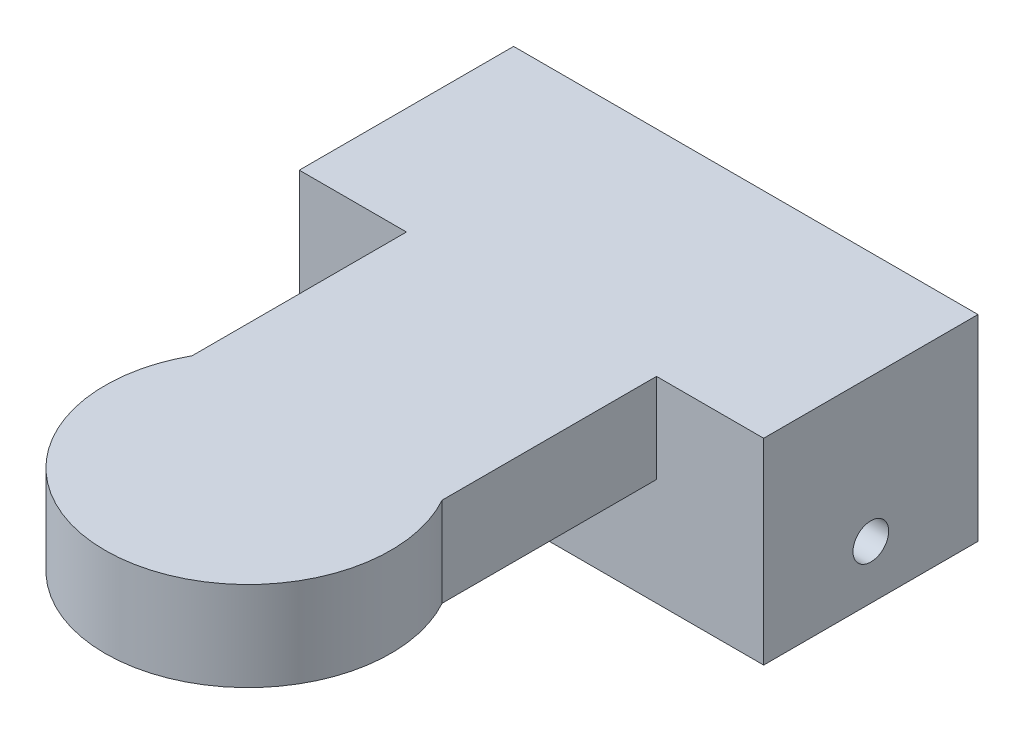
SolidWorks part; units mm, degrees
ref_plane "Front Plane" through (0, 0, 0) normal (0, 0, 1) x (1, 0, 0)
ref_plane "Top Plane" through (0, 0, 0) normal (0, 1, 0) x (1, 0, 0)
ref_plane "Right Plane" through (0, 0, 0) normal (1, 0, 0) x (0, 0, -1)
sketch "Sketch1" plane through (0, 0, 0) normal (0, 1, 0) x (1, 0, 0)
  circle A21 centre (0, 0) radius 20
  dimension "D1" = 40
extrude "Boss-Extrude1" add sketch "Sketch1" along normal blind 10
sketch "Sketch2" plane through (0, 10, 0) normal (0, 1, 0) x (1, 0, 0)
  line L6 (-1.9621, 3.6) -> (1.9621, 3.6)
  line L7 (3.6, 1.9621) -> (3.6, -1.9621)
  arc A3 (-0.6789, -4.0434) -> (3.6, -1.9621) centre (0, 0) ccw
  arc A4 (-1.9621, 3.6) -> (-4.0434, -0.6789) centre (0, 0) ccw
  arc A5 (-4.0434, -0.6789) -> (-0.6789, -4.0434) centre (0, 0) ccw
  arc A6 (3.6, 1.9621) -> (1.9621, 3.6) centre (0, 0) ccw
  point P3 (-1.9621, -3.5912)
  point P4 (-4.1, 0)
  point P5 (0, 0)
  point P6 (0, 0)
  point P19 (0, 3.6)
  dimension "D1" = 3.9243
  dimension "D4" = 4.1
  dimension "D6" = 3.9243
extrude "Cut-Extrude1" cut sketch "Sketch2" against normal through all contours L6 A4 A3 region at (-0.1004, 10, 0.1004)
sketch "Sketch3" plane through (0, 0, 0) normal (0, 1, 0) x (1, 0, 0)
  line L0 (-17.5, 59.6825) -> (-17.5, 9.6825)
  line L1 (-17.5, 59.6825) -> (17.5, 59.6825)
  line L2 (17.5, 59.6825) -> (17.5, 9.6825)
  circle A0 centre (0, 0) radius 20 construction
  arc A1 (17.5, 9.6825) -> (-17.5, 9.6825) centre (0, 0) ccw
  point P6 (0, 59.6825)
  dimension "D1" = 35
  dimension "D2" = 50
extrude "Boss-Extrude2" add sketch "Sketch3" along normal up to surface (10 mm away) up to face at (0, 10, 20)
sketch "Sketch5" plane through (0, 0, 0) normal (0, -1, 0) x (1, 0, 0)
  line L7 (3.6, 1.9621) -> (3.6, -1.9621)
  line L8 (-1.9621, -3.6) -> (1.9621, -3.6)
  circle A0 centre (0, 0) radius 12.5
  arc A6 (1.9621, -3.6) -> (3.6, -1.9621) centre (0, 0) ccw
  arc A7 (3.6, 1.9621) -> (-1.9621, -3.6) centre (0, 0) ccw
  dimension "D1" = 25
extrude "Boss-Extrude3" add sketch "Sketch5" along normal blind 6
sketch "Sketch6" plane through (0, 0, -59.6825) normal (0, 0, -1) x (-1, 0, 0)
  line L0 (-32.5, 10) -> (32.5, 10)
  line L1 (-32.5, 10) -> (-32.5, -15)
  line L2 (-32.5, -15) -> (-22.5, -15)
  line L3 (-22.5, -15) -> (-22.5, 0)
  line L4 (-22.5, 0) -> (22.5, 0)
  line L5 (22.5, 0) -> (22.5, -15)
  line L6 (22.5, -15) -> (32.5, -15)
  line L7 (32.5, -15) -> (32.5, 10)
  line L8 (-17.5, 10) -> (17.5, 10) construction
  line L9 (-17.5, 0) -> (17.5, 0) construction
  point P10 (0, 0)
  dimension "D1" = 45
  dimension "D2" = 10
  dimension "D3" = 15
extrude "Boss-Extrude4" add sketch "Sketch6" against normal blind 20 and the other way blind 10
sketch "Sketch7" plane through (32.5, 0, 0) normal (1, 0, 0) x (0, 0, -1)
  line L0 (39.6825, -15) -> (69.6825, -15) construction
  line L1 (9.6825, 0) -> (39.6825, 0) construction
  circle A0 centre (54.6825, -7.5) radius 2.5
  point P4 (54.6825, -15)
  dimension "D2" = 5
  dimension "D1" = 7.5
extrude "Cut-Extrude2" cut sketch "Sketch7" against normal through all
sketch "Sketch8" plane through (0, 10, 0) normal (0, 1, 0) x (1, 0, 0)
  line L0 (-32.5, 39.6825) -> (-32.5, 69.6825) construction
  line L2 (-32.5, 69.6825) -> (-32.5, 39.6825)
  line L3 (-32.5, 39.6825) -> (-17.5, 39.6825)
  line L4 (32.5, 69.6825) -> (32.5, 39.6825)
  line L6 (17.5, 39.6825) -> (32.5, 39.6825)
  line L8 (-17.5, 39.6825) -> (-17.5, 9.6825)
  line L10 (17.5, 39.6825) -> (17.5, 9.6825)
  line L11 (-32.5, 69.6825) -> (-32.5, 39.6825) construction
  line L12 (-32.5, 69.6825) -> (32.5, 69.6825) construction
  line L13 (32.5, 69.6825) -> (32.5, 39.6825) construction
  line L14 (32.5, 69.6825) -> (-32.5, 69.6825)
  arc A0 (-17.5, 9.6825) -> (17.5, 9.6825) centre (0, 0) ccw
extrude "Boss-Extrude5" add sketch "Sketch8" along normal blind 2.5
sketch "Sketch9" plane through (0, -6, 0) normal (0, -1, 0) x (1, 0, 0)
  circle A0 centre (0, 0) radius 12.5
  circle A1 centre (0, 0) radius 12.5 construction
extrude "Cut-Extrude3" cut sketch "Sketch9" against normal blind 2.5
sketch "Sketch10" plane through (0, 0, -69.6825) normal (0, 0, -1) x (-1, 0, 0)
  line L1 (-22.5, 0) -> (22.5, 0)
  line L2 (-22.5, 0) -> (-22.5, -15)
  line L3 (-22.5, -15) -> (22.5, -15)
  line L4 (22.5, 0) -> (22.5, -15)
extrude "Boss-Extrude6" add sketch "Sketch10" against normal blind 9.95
sketch "Sketch11" plane through (0, 0, -39.6825) normal (0, 0, 1) x (1, 0, 0)
  line L1 (-22.5, 0) -> (22.5, 0)
  line L2 (-22.5, 0) -> (-22.5, -15)
  line L3 (-22.5, -15) -> (22.5, -15)
  line L4 (22.5, 0) -> (22.5, -15)
extrude "Boss-Extrude7" add sketch "Sketch11" against normal blind 9.95
sketch "Sketch12" plane through (0, 0, -69.6825) normal (0, 0, -1) x (-1, 0, 0)
  circle A0 centre (0, -60) radius 47.5
  point P2 (0, -33.544)
  point P4 (0, -54.4375)
  dimension "D1" = 95
  dimension "D2" = 60
extrude "Cut-Extrude4" cut sketch "Sketch12" against normal blind 10
